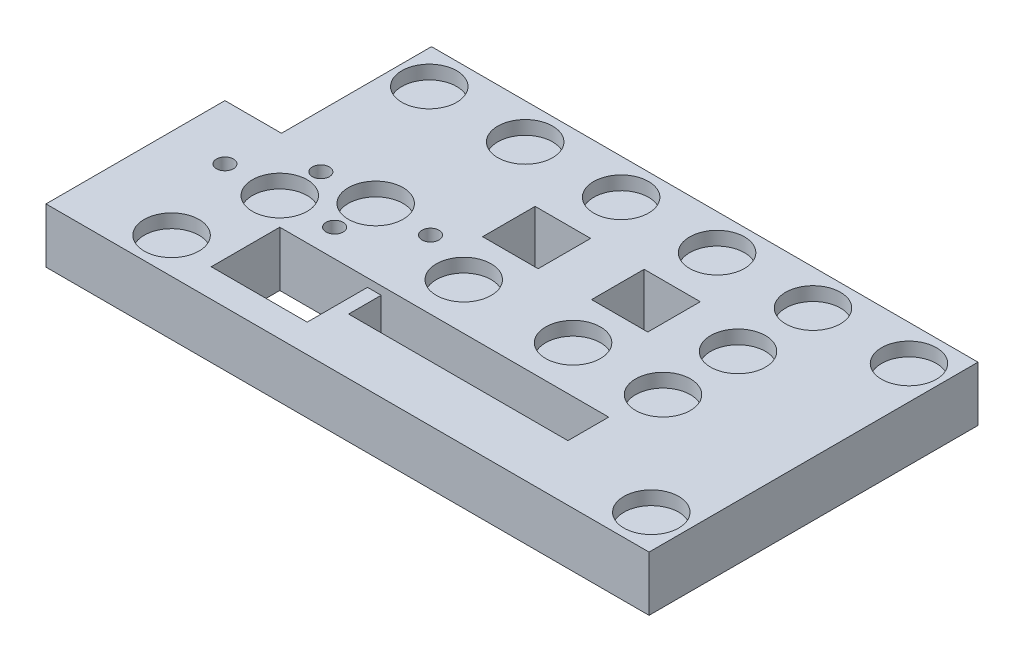
SolidWorks part; units mm, degrees
material "Plain Carbon Steel"
ref_plane "Front Plane" through (0, 0, 0) normal (0, 0, 1) x (1, 0, 0)
ref_plane "Top Plane" through (0, 0, 0) normal (0, 1, 0) x (1, 0, 0)
ref_plane "Right Plane" through (0, 0, 0) normal (1, 0, 0) x (0, 0, -1)
sketch "Sketch1" plane through (0, 0, 0) normal (0, 1, 0) x (1, 0, 0)
  line L1 (-110, -60) -> (110, -60)
  line L2 (-110, -60) -> (-110, 60)
  line L3 (-110, 60) -> (110, 60)
  line L4 (110, -60) -> (110, 60)
  line L5 (-110, -60) -> (110, 60) construction
  line L6 (-110, 60) -> (110, -60) construction
  point P0 (0, 0)
  dimension "D1" = 120
  dimension "D2" = 220
extrude "Boss-Extrude1" add sketch "Sketch1" against normal blind 20
sketch "Sketch2" plane through (0, 0, 0) normal (0, 1, 0) x (1, 0, 0)
  line L1 (-110, 60) -> (-89.3675, 60)
  line L2 (-110, 60) -> (-110, 5.27)
  line L3 (-110, 5.27) -> (-89.3675, 5.27)
  line L4 (-89.3675, 60) -> (-89.3675, 5.27)
  line L5 (-90, -14.72) -> (-89.3675, 5.27) construction
  line L10 (-70, 0.28) -> (-89.3675, 5.27) construction
  circle A0 centre (-90, -14.72) radius 3.1 construction
  circle A1 centre (-70, 0.28) radius 3.1 construction
  dimension "D1" = 20
extrude "Cut-Extrude1" cut sketch "Sketch2" against normal up to next
sketch "Sketch3" plane through (0, 0, 0) normal (0, 1, 0) x (1, 0, 0)
  line L6 (-20, 28.44) -> (-20, 9.28)
  line L7 (-20, 9.28) -> (0.25, 9.28)
  line L8 (0.25, 9.28) -> (0.25, 28.44)
  line L9 (19.75, 28.44) -> (19.75, 9.28)
  line L10 (19.75, 9.28) -> (40.25, 9.28)
  line L11 (40.25, 9.28) -> (40.25, 28.44)
  line L12 (-20, 28.44) -> (0.25, 28.44)
  line L14 (19.75, 28.44) -> (40.25, 28.44)
  line L15 (5.31, 28.5) -> (-15.06, 28.5) construction
  line L18 (40.25, 9.28) -> (40.25, 27.5) construction
  line L19 (19.75, 27.5) -> (19.75, 9.28) construction
  line L20 (19.75, 9.28) -> (40.25, 9.28) construction
  line L21 (0.25, 9.28) -> (0.25, 27.5) construction
  line L22 (-20, 9.28) -> (0.25, 9.28) construction
  line L23 (-20, 27.5) -> (-20, 9.28) construction
  dimension "D1" = 0.06
extrude "Cut-Extrude2" cut sketch "Sketch3" against normal up to next
sketch "Sketch4" plane through (0, 0, 0) normal (0, 1, 0) x (1, 0, 0)
  line L0 (-15.06, -39.66) -> (65.06, -39.66) construction
  line L1 (60, -24.72) -> (-20, -24.72)
  line L2 (60, -24.72) -> (60, -39.6)
  line L3 (60, -39.6) -> (-20, -39.6)
  line L4 (-20, -24.72) -> (-20, -39.6)
  dimension "D1" = 80
  dimension "D2" = 0.06
  dimension "D3" = 14.88
extrude "Cut-Extrude3" cut sketch "Sketch4" against normal up to next
sketch "Sketch8" plane through (0, 0, 0) normal (0, 1, 0) x (1, 0, 0)
  circle A0 centre (-70, 0.28) radius 3.1 construction
  circle A1 centre (-90, -14.72) radius 3.1
  circle A2 centre (-90, -14.72) radius 3.1
  circle A3 centre (-30, 0.28) radius 3.1
  circle A4 centre (-30, 0.28) radius 3.1
  circle A5 centre (-70, 0.28) radius 3.1
  circle A6 centre (-50, -14.72) radius 3.1 construction
  circle A7 centre (-50, -14.72) radius 3.1
  dimension "D1" = 0
  dimension "D2" = 0
extrude "Cut-Extrude4" cut sketch "Sketch8" against normal up to next
sketch "Sketch9" plane through (0, 0, 0) normal (0, 1, 0) x (1, 0, 0)
  line L0 (-20, -27.72) -> (-25, -27.72)
  line L1 (-20, -24.72) -> (-60, -24.72)
  line L2 (-20, -24.72) -> (-20, -27.72)
  line L3 (-25, -49.72) -> (-60, -49.72)
  line L4 (-60, -24.72) -> (-60, -49.72)
  line L5 (-25, -27.72) -> (-25, -49.72)
  dimension "D1" = 25
  dimension "D2" = 5
  dimension "D3" = 35
  dimension "D4" = 3
extrude "Cut-Extrude5" cut sketch "Sketch9" against normal up to next
sketch "Sketch10" plane through (0, 0, 0) normal (0, 1, 0) x (1, 0, 0)
  line L0 (-70, 0.28) -> (-50, 0.28) construction
  line L1 (-50, 0.28) -> (-50, -14.72) construction
  line L2 (-70, 0.28) -> (-70, -14.72) construction
  line L3 (-70, -14.72) -> (-50, -14.72) construction
  line L6 (110, 60) -> (-89.3675, 60) construction
  line L7 (-89.3675, 5.27) -> (-89.3675, 60) construction
  line L8 (110, -60) -> (110, 60) construction
  line L9 (-110, -60) -> (110, -60) construction
  line L10 (-89.3675, 47) -> (110, 47) construction
  line L11 (10.3163, 60) -> (10.3163, -60) construction
  line L12 (30, 9.28) -> (30, -24.72) construction
  line L13 (19.75, 9.28) -> (40.25, 9.28) construction
  line L14 (60, -24.72) -> (-60, -24.72) construction
  line L15 (-9.875, 9.28) -> (-9.875, -24.72) construction
  line L16 (-20, 9.28) -> (0.25, 9.28) construction
  line L17 (62.8163, -7.72) -> (62.8163, 47) construction
  circle A0 centre (-77.1837, 47) radius 10
  circle A1 centre (-42.1837, 47) radius 10
  circle A2 centre (-7.1837, 47) radius 10
  circle A3 centre (27.8163, 47) radius 10
  circle A4 centre (62.8163, 47) radius 10
  circle A5 centre (97.8163, 47) radius 10
  circle A6 centre (30, -7.72) radius 10
  circle A7 centre (62.8163, 19.64) radius 10
  circle A8 centre (-9.875, -7.72) radius 10
  circle A9 centre (97.8163, -47) radius 10
  circle A10 centre (-50, 0.28) radius 10
  circle A11 centre (62.8163, -7.72) radius 10
  circle A12 centre (-70, -14.72) radius 10
  circle A13 centre (-77.1837, -47) radius 10
  point P58 (0, 0)
  point P59 (30, -7.72)
  point P60 (62.8163, 16.8816)
  point P61 (-9.875, -7.72)
  point P62 (62.8163, 19.64)
  dimension "D1" = 20
  dimension "D2" = 175
  dimension "D3" = 35
  dimension "D4" = 35
  dimension "D5" = 13
  dimension "D6" = 13
  dimension "D7" = 35
  dimension "D8" = 35
extrude "Cut-Extrude6" cut sketch "Sketch10" against normal blind 5 and the other way through all
